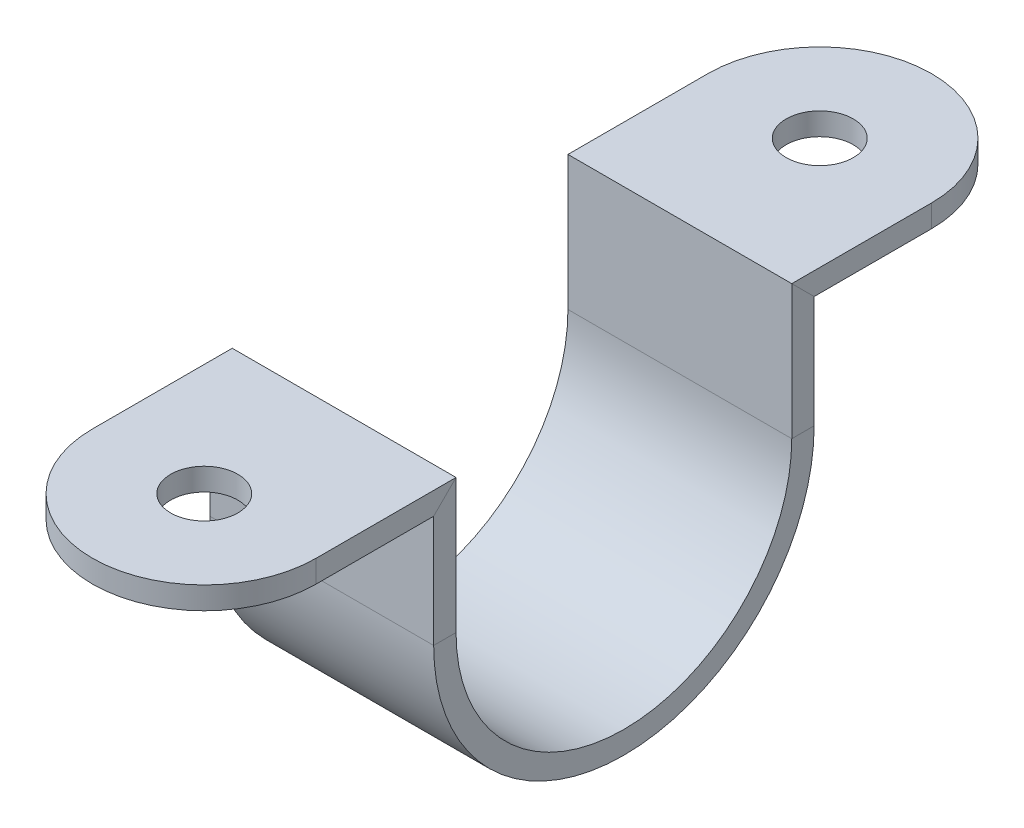
SolidWorks part; units mm, degrees
ref_plane "Front Plane" through (0, 0, 0) normal (0, 0, 1) x (1, 0, 0)
ref_plane "Top Plane" through (0, 0, 0) normal (0, 1, 0) x (1, 0, 0)
ref_plane "Right Plane" through (0, 0, 0) normal (1, 0, 0) x (0, 0, -1)
sketch "Sketch1" plane through (0, 0, 0) normal (1, 0, 0) x (0, 0, -1)
  line L0 (0, 0) -> (11.25, 0)
  line L1 (11.25, 0) -> (11.25, -6)
  line L3 (26.25, -6) -> (26.25, 0)
  line L4 (26.25, 0) -> (37.5, 0)
  arc A0 (11.25, -6) -> (26.25, -6) centre (18.75, -6) ccw
  dimension "D1" = 15
  dimension "D2" = 6
  dimension "D3" = 37.5
sketch "Sketch2" plane through (0, 0, 0) normal (0, 0, 1) x (1, 0, 0)
  line L1 (-5, 0) -> (5, 0)
  line L2 (-5, 0) -> (-5, -1)
  line L3 (-5, -1) -> (5, -1)
  line L4 (5, 0) -> (5, -1)
  dimension "D1" = 1
  dimension "D2" = 10
sweep "Sweep1" add profiles "Sketch2" path "Sketch1"
fillet "Fillet3" 2 edges at (5, -0.5, 0) (-5, -0.5, 0) type full round first side face at (5, -0.5, -5.375) second side face at (-5, -0.5, -5.375) middle face at (0, -0.5, 0)
fillet "Fillet4" 2 edges at (-5, -0.5, -37.5) (5, -0.5, -37.5) type full round first side face at (-5, -0.5, -32.125) second side face at (5, -0.5, -32.125) middle face at (0, -0.5, -37.5)
sketch "Sketch3" plane through (0, 0, 0) normal (0, 1, 0) x (1, 0, 0)
  line L0 (0, 18.75) -> (0, 32.5) construction
  line L1 (0, 18.75) -> (0, 5) construction
  line L2 (5, 11.25) -> (5, 26.25) construction
  circle A0 centre (0, 5) radius 1.5
  circle A1 centre (0, 32.5) radius 1.5
  point P7 (5, 18.75)
  dimension "D2" = 3
  dimension "D1" = 27.5
extrude "Cut-Extrude1" cut sketch "Sketch3" against normal through all both and the other way through all
